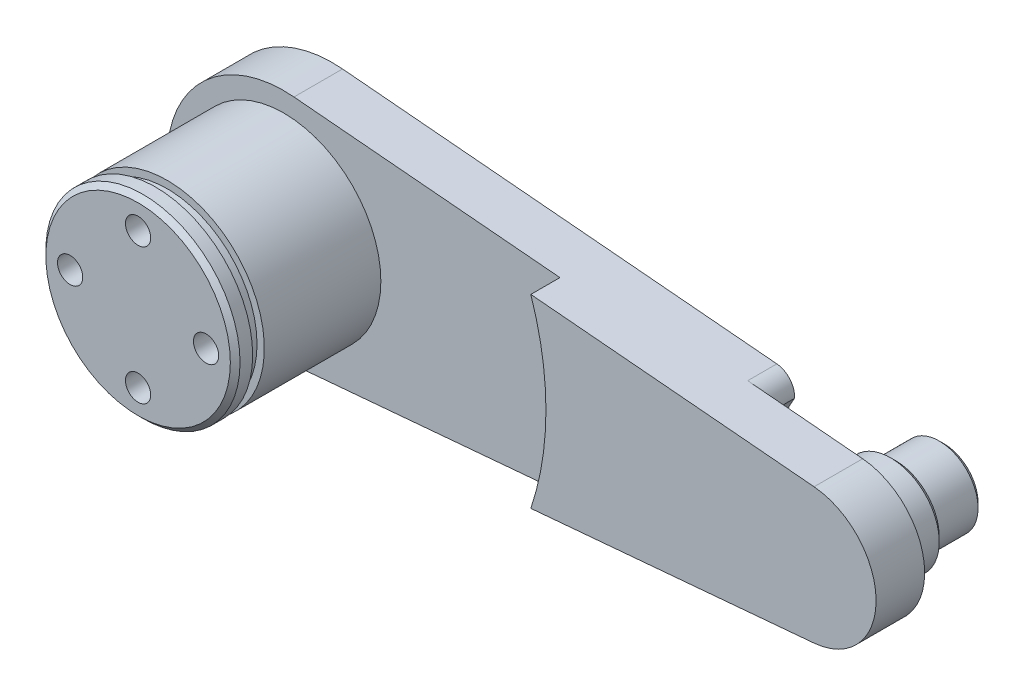
SolidWorks part; units mm, degrees
material "PEI"
ref_plane "前视基准面" through (0, 0, 0) normal (0, 0, 1) x (1, 0, 0)
ref_plane "上视基准面" through (0, 0, 0) normal (0, 1, 0) x (1, 0, 0)
ref_plane "右视基准面" through (0, 0, 0) normal (1, 0, 0) x (0, 0, -1)
other "Configuration Table"
sketch "草图1" plane through (0, 0, 0) normal (0, 0, 1) x (1, 0, 0)
  line L0 (0, 0) -> (57, 0) construction
  line L1 (1.0526, 11.9537) -> (57.614, 6.973)
  line L2 (1.0526, -11.9537) -> (57.614, -6.973)
  circle A0 centre (0, 0) radius 12
  circle A1 centre (57, 0) radius 7
  dimension "D2" = 24
  dimension "D3" = 14
  dimension "D1" = 57
extrude "凸台-拉伸1" add sketch "草图1" along normal blind 5 contours A0 L0 A1 | A0 | L0 A0 A1 | A1 region at (29.2817, 5.0036, 0) region at (8.5993, -7.8753, 0) region at (29.2817, -5.0036, 0) region at (52.406, 5.0163, 0)
sketch "草图2" plane through (0, 0, 5) normal (0, 0, 1) x (1, 0, 0)
  arc A0 (1.0526, 11.9537) -> (1.0526, -11.9537) centre (0, 0) ccw construction
  arc A1 (1.0526, 11.9537) -> (1.0526, -11.9537) centre (0, 0) ccw
  circle A2 centre (0, 0) radius 12
  circle A3 centre (0, 0) radius 10
  dimension "D1" = 20
extrude "凸台-拉伸2" add sketch "草图2" along normal blind 15 contours A3 region at (0, 0, 5)
sketch "草图3" plane through (0, 0, 0) normal (0, 0, -1) x (-1, 0, 0)
  arc A0 (-57.614, 6.973) -> (-57.614, -6.973) centre (-57, 0) ccw construction
  arc A1 (-57.614, 6.973) -> (-57.614, -6.973) centre (-57, 0) ccw
  circle A2 centre (-57, 0) radius 4
  dimension "D1" = 8
extrude "凸台-拉伸3" add sketch "草图3" along normal blind 6 contours A2 region at (57, 0, 0)
sketch "草图4" plane through (0, 0, 0) normal (0, 0, -1) x (-1, 0, 0)
  circle A0 centre (-57, 0) radius 4 construction
  circle A1 centre (-57, 0) radius 4
  circle A2 centre (-57, 0) radius 5
  dimension "D1" = 1
extrude "凸台-拉伸4" add sketch "草图4" along normal blind 1
chamfer "倒角1" distance 0.5 angle 45 3 edges at (10, 0, 20) (52, 0, -1) (53, 0, -6)
sketch "草图6" plane through (0, 0, 20) normal (0, 0, 1) x (1, 0, 0)
  circle A0 centre (0, 0) radius 7 construction
  circle A1 centre (0, 7) radius 1.3
  circle A2 centre (7, 0) radius 1.3
  circle A3 centre (0, -7) radius 1.3
  circle A4 centre (-7, 0) radius 1.3
  point P14 (0, 0)
  dimension "D1" = 14
  dimension "D2" = 2.6
  dimension "D3" = 4
extrude "切除-拉伸2" cut sketch "草图6" against normal blind 6
sketch "草图11" plane through (0, 0, -6) normal (0, 0, -1) x (-1, 0, 0)
  circle A0 centre (-57, 0) radius 2.2
  dimension "D1" = 4.4
extrude "切除-拉伸7" cut sketch "草图11" against normal blind 10
sketch "草图12" plane through (0, 0, 5) normal (0, 0, 1) x (1, 0, 0)
  line L0 (0.8772, 9.9615) -> (57.4386, 4.9807)
  line L1 (0.8772, -9.9615) -> (57.4386, -4.9807)
  circle A0 centre (57, 0) radius 5 construction
  circle A1 centre (0, 0) radius 10 construction
  circle A2 centre (57, 0) radius 5
  circle A3 centre (0, 0) radius 10
  circle A4 centre (0, 0) radius 12
  circle A6 centre (57, 0) radius 2.6568
  dimension "D1" = 2
extrude "切除-拉伸8" cut sketch "草图12" against normal blind 5 contours A6 L0 A4 L1 region at (30.098, 0, 5)
sketch "草图14" plane through (0, 0, 0) normal (0, 0, -1) x (-1, 0, 0)
  circle A0 centre (-57, 0) radius 11.075
  circle A1 centre (-57, 0) radius 5 construction
  circle A2 centre (-57, 0) radius 5
  arc M2 (-57.4386, -4.9807) -> (-57.4386, 4.9807) centre (-57, 0) cw
  line M3 (-57.614, -6.973) -> (-1.0526, -11.9537)
  line M5 (-1.0526, 11.9537) -> (-57.614, 6.973)
  arc M6 (-57.614, 6.973) -> (-57.614, -6.973) centre (-57, 0) ccw
  dimension "D1" = 22.15
extrude "切除-拉伸9" cut sketch "草图14" against normal blind 3 contours A0 M5 M3 M6 | A0 M3 M5 M6 M2 region at (46.9602, -4.0802, 0) region at (53.365, 7.6402, 0)
sketch "草图15" plane through (0, 0, 5) normal (0, 0, 1) x (1, 0, 0)
  line L6 (1.0526, -11.9537) -> (57.614, -6.973)
  line L7 (57.614, 6.973) -> (1.0526, 11.9537)
  line L8 (1.0526, -11.9537) -> (57.614, -6.973)
  line L9 (57.614, 6.973) -> (1.0526, 11.9537)
  arc A6 (57.614, -6.973) -> (57.614, 6.973) centre (57, 0) ccw
  arc A7 (1.0526, 11.9537) -> (1.0526, -11.9537) centre (0, 0) ccw
  arc A8 (57.614, -6.973) -> (57.614, 6.973) centre (57, 0) ccw
  arc A9 (1.0526, 11.9537) -> (1.0526, -11.9537) centre (0, 0) ccw
  circle M1 centre (0, 0) radius 10
  line M2 (1.0526, -11.9537) -> (57.614, -6.973)
  arc M3 (57.614, -6.973) -> (57.614, 6.973) centre (57, 0) ccw
  line M4 (57.614, 6.973) -> (1.0526, 11.9537)
  arc M5 (1.0526, 11.9537) -> (1.0526, -11.9537) centre (0, 0) ccw
  line M6 (7.4849, 9.3796) -> (57.4386, 4.9807)
  line M8 (57.4386, -4.9807) -> (7.4849, -9.3796)
  arc M9 (7.4849, -9.3796) -> (7.4849, 9.3796) centre (0, 0) ccw
  dimension "D1" = 0
extrude "凸台-拉伸5" add sketch "草图15" against normal blind 1 contours M6 M8 | M5 M2 M3 M4 M9 M6 M8 M1 region at (29.4855, 0, 5)
fillet "圆角1" radius 2 2 edges at (49.0648, -7.7258, 1.5) (49.0648, 7.7258, 1.5)
sketch "草图16" plane through (0, 0, 0) normal (0, 1, 0) x (1, 0, 0)
  line L0 (-9.5, -20) -> (9.5, -20) construction
  line L1 (9.25, -17) -> (13.9131, -17)
  line L2 (9.25, -17) -> (9.25, -18.2)
  line L3 (9.25, -18.2) -> (13.9131, -18.2)
  line L4 (13.9131, -17) -> (13.9131, -18.2)
  line L5 (0, -20) -> (0, 0) construction
  dimension "D1" = 1.2
  dimension "D2" = 3
  dimension "D3" = 9.25
revolve "切除-旋转1" cut sketch "草图16" angle 360 about L5
sketch "草图17" plane through (0, 0, 4) normal (0, 0, -1) x (-1, 0, 0)
  line L2 (-7.4849, 9.3796) -> (-57.4386, 4.9807)
  line L3 (-57.4386, -4.9807) -> (-7.4849, -9.3796)
  line L4 (-7.4849, 9.3796) -> (-47.5946, 5.8476)
  line L5 (-47.5946, -5.8476) -> (-7.4849, -9.3796)
  line L9 (-43.5635, 2.1558) -> (-43.5635, -2.1558)
  line L10 (-43.5635, -2.1558) -> (-15.3448, -4.6407)
  line L11 (-15.3448, 4.6407) -> (-43.5635, 2.1558)
  line L14 (-47.5946, 5.8476) -> (-47.5946, -5.8476) construction
  arc A2 (-7.4849, 9.3796) -> (-7.4849, -9.3796) centre (0, 0) ccw
  arc A3 (-57.4386, -4.9807) -> (-57.4386, 4.9807) centre (-57, 0) ccw
  arc A4 (-7.4849, 9.3796) -> (-7.4849, -9.3796) centre (0, 0) ccw
  arc A6 (-57.4386, -4.9807) -> (-57.4386, 4.9807) centre (-57, 0) ccw
  arc A7 (-45.7778, 8.0153) -> (-47.5946, 5.8476) centre (-45.6023, 6.023) ccw construction
  arc A8 (-45.7778, 8.0153) -> (-47.5946, 5.8476) centre (-45.6023, 6.023) ccw
  arc A10 (-15.3448, 4.6407) -> (-15.3448, -4.6407) centre (0, 0) ccw
  arc A11 (-47.5946, -5.8476) -> (-47.5946, 5.8476) centre (-57, 0) ccw
  arc M5 (-7.4849, -9.3796) -> (-7.4849, 9.3796) centre (0, 0) cw
  line M6 (-7.4849, 9.3796) -> (-57.4386, 4.9807)
  line M8 (-57.4386, -4.9807) -> (-7.4849, -9.3796)
  dimension "D1" = 0
extrude "凸台-拉伸6" add sketch "草图17" along normal up to surface (4 mm away) contours A10 L11 L9 L10 | A11 L11 A10 L10 L9 M8 M5 M6 region at (12.4428, 0, 4) region at (28.0102, 0, 4) up to face at (24.5225, 0, 0)
sketch "草图18" plane through (0, 0, 4) normal (0, 0, -1) x (-1, 0, 0)
  line L4 (-47.5946, 5.8476) -> (-57.4386, 4.9807)
  line L5 (-57.4386, -4.9807) -> (-47.5946, -5.8476)
  line L7 (-47.5946, 5.8476) -> (-57.4386, 4.9807)
  line L8 (-57.4386, -4.9807) -> (-47.5946, -5.8476)
  arc A1 (-57.4386, -4.9807) -> (-57.4386, 4.9807) centre (-57, 0) ccw
  arc A4 (-57.4386, -4.9807) -> (-57.4386, 4.9807) centre (-57, 0) ccw
  arc A6 (-47.5946, -5.8476) -> (-47.5946, 5.8476) centre (-57, 0) ccw
  arc A10 (-47.5946, -5.8476) -> (-47.5946, 5.8476) centre (-57, 0) ccw
  dimension "D1" = 0
extrude "凸台-拉伸7" add sketch "草图18" along normal up to surface (1 mm away) up to face at (53.5869, 0, 3)
sketch "草图19" plane through (0, 0, 5) normal (0, 0, 1) x (1, 0, 0)
  line L2 (1.0526, -11.9537) -> (57.614, -6.973)
  line L3 (57.614, 6.973) -> (1.0526, 11.9537)
  line L4 (28.4421, -9.5419) -> (57.614, -6.973)
  line L5 (57.614, 6.973) -> (28.4421, 9.5419)
  arc A0 (28.4421, -9.5419) -> (28.4421, 9.5419) centre (0, 0) ccw
  arc A2 (57.614, -6.973) -> (57.614, 6.973) centre (57, 0) ccw
  arc A3 (1.0526, 11.9537) -> (1.0526, -11.9537) centre (0, 0) ccw
  arc A4 (57.614, -6.973) -> (57.614, 6.973) centre (57, 0) ccw
  dimension "D2" = 60
  dimension "D1" = 0
extrude "凸台-拉伸8" add sketch "草图19" along normal blind 3
equation "\"D1@草图1\"= \"主动杆_前_长度\""
equation "\"主动杆_前_长度\"= 57"
